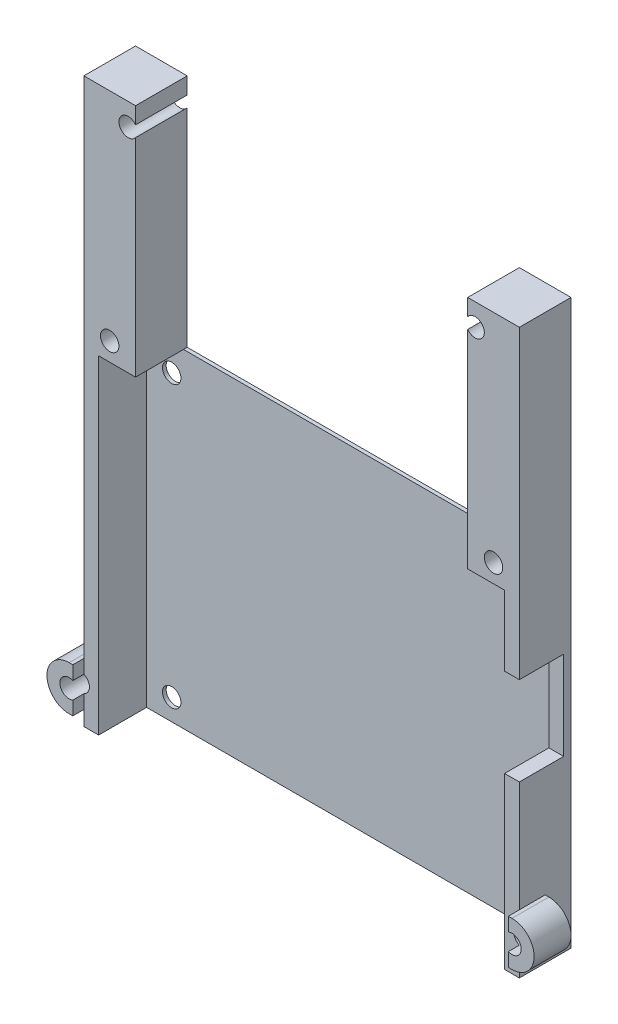
SolidWorks part; units mm, degrees
ref_plane "Front Plane" through (0, 0, 0) normal (0, 0, 1) x (1, 0, 0)
ref_plane "Top Plane" through (0, 0, 0) normal (0, 1, 0) x (1, 0, 0)
ref_plane "Right Plane" through (0, 0, 0) normal (1, 0, 0) x (0, 0, -1)
sketch "Sketch1" plane through (0, 0, 0) normal (0, 1, 0) x (1, 0, 0)
  line L0 (0, 0) -> (2, 0)
  line L1 (0, 0) -> (59, 0) construction
  line L2 (0, 0) -> (0, 7)
  line L3 (0, 7) -> (59, 7)
  line L4 (59, 0) -> (59, 7)
  line L5 (2, 0) -> (2, 6.5)
  line L6 (2, 6.5) -> (57, 6.5)
  line L7 (57, 6.5) -> (57, 0)
  line L8 (57, 0) -> (59, 0)
  dimension "D1" = 59
  dimension "D2" = 7
  dimension "D3" = 2
  dimension "D4" = 6.5
  dimension "D5" = 55
extrude "Boss-Extrude1" add sketch "Sketch1" along normal blind 44.5
sketch "Sketch2" plane through (59, 0, 0) normal (1, 0, 0) x (0, 0, -1)
  line L0 (0, 0) -> (0, 23) construction
  line L1 (0, 44.5) -> (0, 0) construction
  line L2 (0, 23) -> (6, 23)
  line L3 (6, 23) -> (6, 35)
  line L4 (6, 35) -> (0, 35)
  line L5 (0, 35) -> (0, 23)
  dimension "D1" = 23
  dimension "D2" = 6
  dimension "D3" = 12
extrude "Cut-Extrude1" cut sketch "Sketch2" against normal blind 10
sketch "Sketch3" plane through (0, 0, -7) normal (0, 0, -1) x (-1, 0, 0)
  line L0 (-59, 0) -> (-59, 8) construction
  line L1 (-59, 44.5) -> (-59, 0) construction
  line L2 (-59, 8) -> (-59, 2)
  line L3 (-59, 5) -> (-59.5, 5) construction
  line L4 (-59, 8) -> (-59.5, 8)
  line L5 (-59, 2) -> (-59.5, 2)
  line L6 (0, 0) -> (0, 8) construction
  line L7 (0, 44.5) -> (0, 0) construction
  line L8 (0, 8) -> (0.5, 8)
  line L9 (0, 8) -> (0, 2)
  line L10 (0, 2) -> (0.5, 2)
  line L11 (0, 5) -> (0.5, 5) construction
  arc A0 (-59.5, 8) -> (-59.5, 2) centre (-59.5, 5) ccw
  circle A1 centre (-59.5, 5) radius 1.25
  arc A2 (0.5, 8) -> (0.5, 2) centre (0.5, 5) cw
  circle A3 centre (0.5, 5) radius 1.25
  line M5 (0, 0) -> (0, 44.5)
  line M7 (-59, 44.5) -> (-59, 0)
  dimension "D4" = 3
  dimension "D5" = 2.5
  dimension "D11" = 3
  dimension "D12" = 2.5
  dimension "D1" = 8
  dimension "D2" = 6
  dimension "D3" = 0.5
  dimension "D6" = 8
  dimension "D7" = 0.5
  dimension "D8" = 6
  dimension "D9" = 0.5
extrude "Boss-Extrude2" add sketch "Sketch3" against normal blind 8.5 contours A1 L4 A0 L5 M7 | A3 L10 A2 L8 M5 region at (59.0695, 7.0728, -7) region at (-0.25, 7.9305, -7)
extrude "Cut-Extrude2" cut sketch "Sketch3<3>" against normal blind 11 contours L2 A1 | L9 A3 region at (58.6906, 5, -7) region at (0.3094, 5, -7)
sketch "Sketch3<3>" plane through (0, 0, -7) normal (0, 0, -1) x (-1, 0, 0) same geometry as "Sketch3"
sketch "Sketch4" plane through (0, 44.5, 0) normal (0, 1, 0) x (1, 0, 0)
  line L0 (59, 7) -> (0, 7) construction
  line L1 (0, 0) -> (7, 0)
  line L2 (0, 0) -> (0, 7)
  line L3 (0, 7) -> (7, 7)
  line L4 (7, 0) -> (7, 7)
  line L6 (59, 0) -> (52, 0)
  line L7 (59, 0) -> (59, 7)
  line L8 (59, 7) -> (52, 7)
  line L9 (52, 0) -> (52, 7)
  dimension "D1" = 7
  dimension "D2" = 7
extrude "Boss-Extrude3" add sketch "Sketch4" along normal blind 5
sketch "Sketch9" plane through (0, 49.5, 0) normal (0, 1, 0) x (1, 0, 0)
  line L1 (0, 0) -> (7, 0)
  line L2 (0, 0) -> (0, 7)
  line L3 (0, 7) -> (7, 7)
  line L4 (7, 0) -> (7, 7)
  line L5 (52, 0) -> (59, 0)
  line L6 (52, 0) -> (52, 7)
  line L7 (52, 7) -> (59, 7)
  line L8 (59, 0) -> (59, 7)
extrude "Boss-Extrude5" add sketch "Sketch9" along normal blind 26.85
sketch "Sketch5" plane through (0, 0, -7) normal (0, 0, -1) x (-1, 0, 0)
  line L0 (-59, 49.5) -> (-52, 44.5) construction
  line L1 (0, 49.5) -> (-7, 44.5) construction
  line L2 (-53, 73.35) -> (-6, 73.35) construction
  line L3 (-6, 73.35) -> (-6, 47) construction
  line L4 (-6, 47) -> (-3.5, 47) construction
  line L5 (-52, 76.35) -> (-52, 44.5) construction
  line L6 (-29.5, 73.35) -> (-29.5, -5.4278) construction
  circle A0 centre (-55.5, 47) radius 1.25
  circle A1 centre (-3.5, 47) radius 1.25
  circle A2 centre (-6, 73.35) radius 1.25
  circle A3 centre (-53, 73.35) radius 1.25
  point P23 (0, 0)
  dimension "D1" = 2.5
  dimension "D3" = 2.5
  dimension "D4" = 3.5
extrude "Cut-Extrude3" cut sketch "Sketch5" against normal through all
sketch "Sketch7" plane through (0, 0, -7) normal (0, 0, -1) x (-1, 0, 0)
  line L0 (-59, 0) -> (-59, 2.9) construction
  line L1 (-59, 2) -> (-59, 0) construction
  line L2 (-59, 2.9) -> (0, 2.9) construction
  line L3 (0, 2) -> (0, 0) construction
  line L4 (-53.6, 2.9) -> (-5.4, 2.9)
  line L5 (-53.6, 2.9) -> (-53.6, 40.95) construction
  line L6 (-53.6, 40.95) -> (-5.4, 40.95) construction
  circle A0 centre (-53.6, 2.9) radius 1.25
  circle A1 centre (-5.4, 2.9) radius 1.25
  circle A2 centre (-53.6, 40.95) radius 1.25
  circle A3 centre (-5.4, 40.95) radius 1.25
  point P11 (-29.5, 2.9)
  dimension "D3" = 2.5
  dimension "D4" = 2.5
  dimension "D6" = 2.5
  dimension "D8" = 2.5
  dimension "D1" = 2.9
  dimension "D2" = 48.2
  dimension "D5" = 38.05
  dimension "D7" = 48.2
extrude "Cut-Extrude4" cut sketch "Sketch7" against normal blind 10 contours A2 | A3 | A1 | A0 region at (5.4, 4.1146, -7) region at (54.8146, 2.9, -7) region at (53.6, 40.95, -7) region at (5.4, 40.95, -7)
extrude "Cut-Extrude6" cut sketch "Sketch3<4>" against normal blind 3.5 contours A1 L4 A0 L5 M7 | A3 L10 A2 L8 M5 region at (59.0695, 7.0728, -7) region at (-0.25, 7.9305, -7)
sketch "Sketch3<4>" plane through (0, 0, -7) normal (0, 0, -1) x (-1, 0, 0) same geometry as "Sketch3"
extrude "Boss-Extrude4" add sketch "Sketch3<5>" against normal blind 3 contours L9 A3 | L2 A1 region at (58.6906, 5, -7) region at (0.3094, 5, -7)
sketch "Sketch3<5>" plane through (0, 0, -7) normal (0, 0, -1) x (-1, 0, 0) same geometry as "Sketch3"
